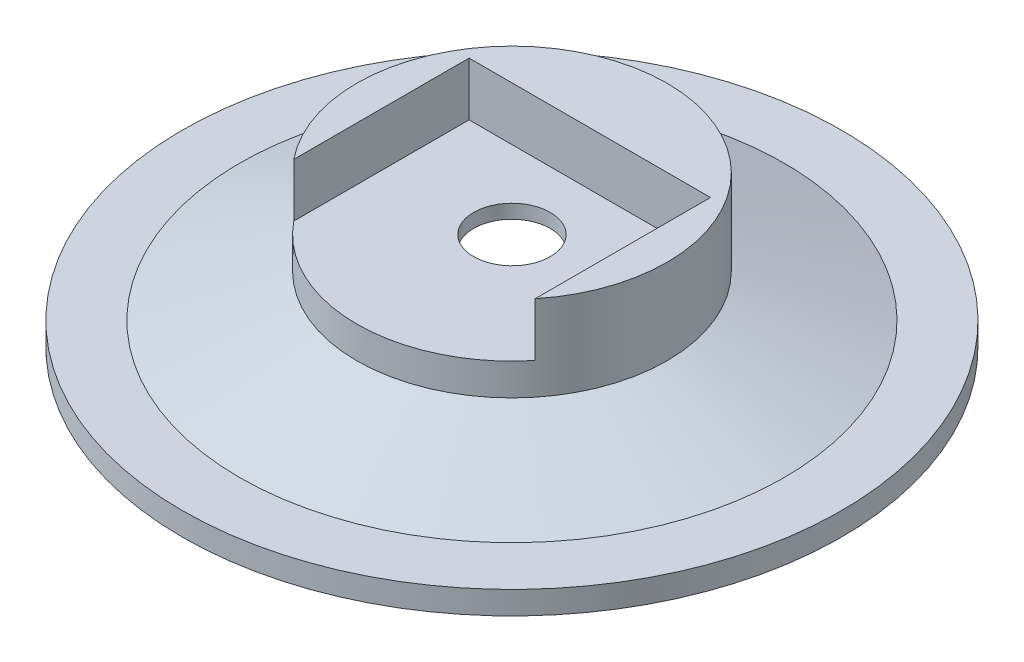
SolidWorks part; units mm, degrees
ref_plane "Front Plane" through (0, 0, 0) normal (0, 0, 1) x (1, 0, 0)
ref_plane "Top Plane" through (0, 0, 0) normal (0, 1, 0) x (1, 0, 0)
ref_plane "Right Plane" through (0, 0, 0) normal (1, 0, 0) x (0, 0, -1)
sketch "Sketch3" plane through (0, 0, 0) normal (0, 0, 1) x (1, 0, 0)
  line L0 (0, 0) -> (17.5, 0) construction
  line L1 (0, 6.35) -> (17.5, 6.35) construction
  line L2 (17.5, 0) -> (2.5, 5.4429)
  line L3 (2.5, -13.9932) -> (2.5, 1.2597) construction
  line L4 (0, 0) -> (0, -13.9932) construction
  line L5 (17.5, 0) -> (21.5, 0)
  line L6 (2.5, 9.8395) -> (2.5, 5.4429)
  line L7 (17.7637, 1.5) -> (21.5, 1.5)
  line L8 (17.7637, 1.5) -> (10.12, 4.2736)
  line L9 (21.5, 1.5) -> (21.5, 0)
  line L10 (10.12, 9.8395) -> (10.12, 4.2736)
  line L11 (10.12, 9.8395) -> (2.5, 9.8395)
  line L12 (2.5, 5.4429) -> (2.5, 9.8395) construction
  line L13 (17.7637, 1.5) -> (0.5116, 7.76) construction
  line L14 (17.5, 0) -> (0, 6.35) construction
  dimension "D1" = 17.5
  dimension "D2" = 6.35
  dimension "D3" = 2.5
  dimension "D4" = 4
  dimension "D6" = 7.62
  dimension "D5" = 1.5
revolve "Revolve1" add sketch "Sketch3" angle 360 about L4
sketch "Sketch for side slot DNU" plane through (0, 0, 0) normal (0, 0, 1) x (1, 0, 0)
  line L0 (0, 0) -> (0, 18.8028) construction
  line L1 (0, 0) -> (-24.5114, 0) construction
  line L2 (-7.874, 8.382) -> (7.874, 8.382)
  line L3 (-7.874, 8.382) -> (-7.874, 9.398)
  line L4 (-7.874, 9.398) -> (7.874, 9.398)
  line L5 (7.874, 8.382) -> (7.874, 9.398)
  line L6 (-7.874, 8.382) -> (7.874, 9.398) construction
  line L7 (-7.874, 9.398) -> (7.874, 8.382) construction
  point P3 (0, 8.89)
  dimension "D1" = 15.748
  dimension "D2" = 1.016
  dimension "D3" = 8.89
ref_plane "Plane4" through (0, 12.7, 0) normal (0, 1, 0) x (1, 0, 0)
sketch "Sketch5" plane through (0, 12.7, 0) normal (0, 1, 0) x (1, 0, 0)
  line L0 (0, 0) -> (35.335, 0) construction
  line L1 (0, 0) -> (0, 26.2568) construction
  line L2 (7.874, 5.08) -> (-7.874, 5.08)
  line L3 (-7.874, 5.08) -> (-7.874, -10.668)
  line L4 (-7.874, -10.668) -> (7.874, -10.668)
  line L5 (7.874, -10.668) -> (7.874, 5.08)
  point P7 (0, 5.08)
  dimension "D1" = 15.748
  dimension "D2" = 15.748
  dimension "D3" = 5.08
extrude "Cut-Extrude1" cut sketch "Sketch5" against normal blind 6.35
